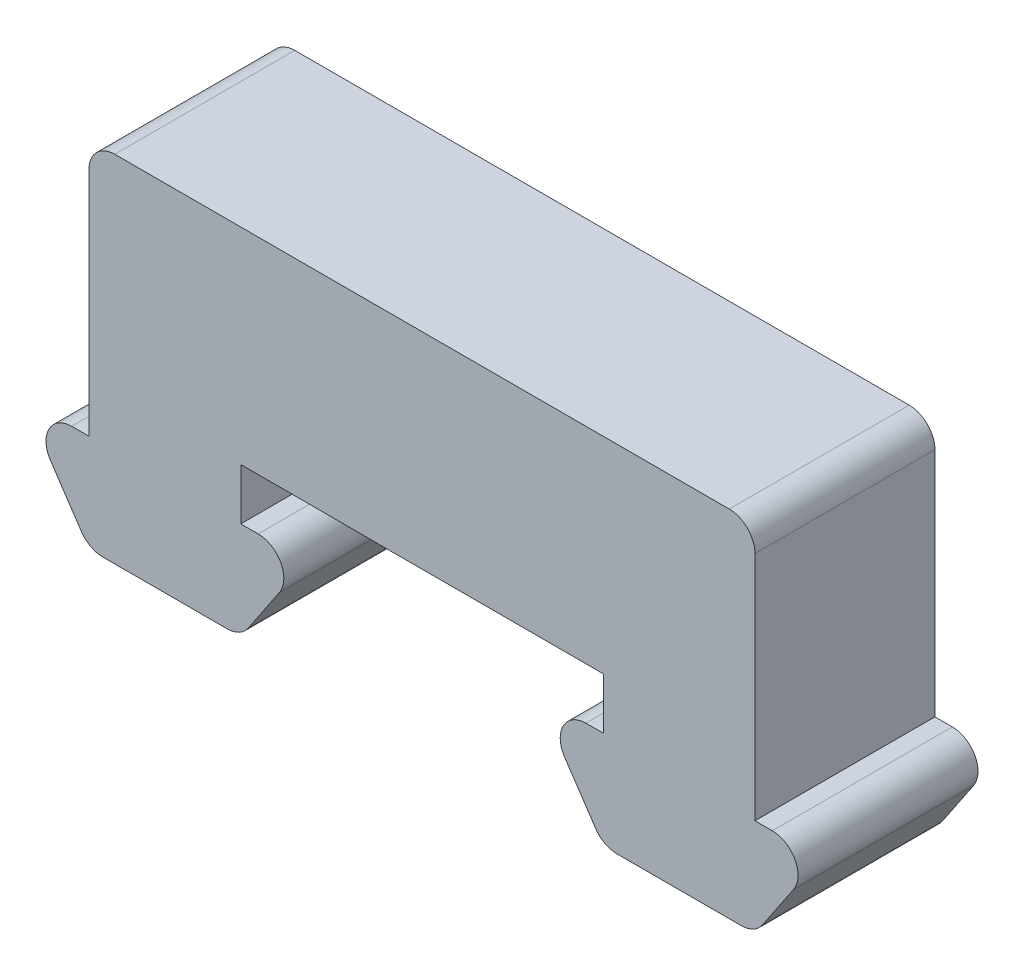
SolidWorks part; units mm, degrees
ref_plane "Front Plane" through (0, 0, 0) normal (0, 0, 1) x (1, 0, 0)
ref_plane "Top Plane" through (0, 0, 0) normal (0, 1, 0) x (1, 0, 0)
ref_plane "Right Plane" through (0, 0, 0) normal (1, 0, 0) x (0, 0, -1)
sketch "Sketch1" plane through (0, 0, 0) normal (0, 0, 1) x (1, 0, 0)
  line L0 (10, 0) -> (-10, 0) construction
  line L2 (-4.5, 0) -> (-15.5, 0)
  line L4 (-7.05, -3.8) -> (-12.95, -3.8)
  line L5 (-12.95, -3.8) -> (-15.5, 0)
  line L6 (-7.05, -3.8) -> (-4.5, 0)
  line L7 (0, 10.7085) -> (0, -11.1808) construction
  line L8 (-12.95, 0) -> (-12.95, 2)
  line L9 (-7.05, 0) -> (-7.05, 2)
  line L10 (-7.05, 2) -> (7.05, 2) construction
  line L11 (-12.95, 2) -> (-12.95, 10)
  line L12 (-4.6, 8.5) -> (4.6, 8.5)
  line L13 (-4.6, 8.5) -> (-4.6, 2)
  line L14 (-4.6, 2) -> (4.6, 2)
  line L16 (-4.6, 8.5) -> (0, 5.25) construction
  line L17 (-4.6, 2) -> (0, 5.25) construction
  line L18 (-12.95, 10) -> (12.95, 10)
  line L19 (4.6, 2) -> (0, 5.25) construction
  line L20 (4.6, 8.5) -> (0, 5.25) construction
  line L21 (4.6, 8.5) -> (4.6, 2)
  line L22 (12.95, 2) -> (12.95, 10)
  line L23 (7.05, 0) -> (7.05, 2)
  line L24 (12.95, 0) -> (12.95, 2)
  line L25 (7.05, -3.8) -> (4.5, 0)
  line L26 (12.95, -3.8) -> (15.5, 0)
  line L27 (7.05, -3.8) -> (12.95, -3.8)
  line L28 (4.5, 0) -> (15.5, 0)
  line L29 (4.6, 2) -> (7.05, 2)
  line L30 (-7.05, 2) -> (-4.6, 2)
  point P4 (0, 0)
  point P8 (-10, 0)
  point P10 (-10, -3.8)
  point P16 (0, 5.25)
  point P17 (0, 8.5)
  point P23 (0, 2)
  point P28 (0, 10)
  point P35 (10, 0)
  dimension "D1" = 20
  dimension "D2" = 5.5
  dimension "D3" = 5.9
  dimension "D4" = 3.8
  dimension "D5" = 2
  dimension "D6" = 6.5
  dimension "D7" = 4.6
  dimension "D8" = 1.5
extrude "Boss-Extrude1" add sketch "Sketch1" along normal blind 5 contours L9 L30 L13 L12 L21 L29 L23 L28 L24 L22 L18 L11 L8 L2 | L4 L6 L2 L5 | L28 L25 L27 L26 region at (-10, -1.7089, 0) region at (-10, 0.2776, 0) region at (10, -1.7089, 0)
extrude "Boss-Extrude2" add sketch "Sketch1<3>" along normal blind 2 from surface contours L21 L12 L13 L14 | L9 L30 L13 L12 L21 L29 L23 L28 L24 L22 L18 L11 L8 L2 | L4 L6 L2 L5 | L28 L25 L27 L26 region at (-10, -1.7089, 0) region at (-10, 0.2776, 0) region at (0, 5.25, 0) region at (10, -1.7089, 0) starting at face at (0, 1.49, 5)
sketch "Sketch1<3>" plane through (0, 0, 0) normal (0, 0, 1) x (1, 0, 0) same geometry as "Sketch1"
fillet "Fillet1" radius 1 12 edges at (-4.6, 2, 2.5) (4.6, 2, 2.5) (-4.5, 0, 3.5) (-7.05, -3.8, 3.5) (-12.95, -3.8, 3.5) (-15.5, 0, 3.5) (-12.95, 10, 3.5) (12.95, 10, 3.5) (15.5, 0, 3.5) (12.95, -3.8, 3.5) (7.05, -3.8, 3.5) (4.5, 0, 3.5)
